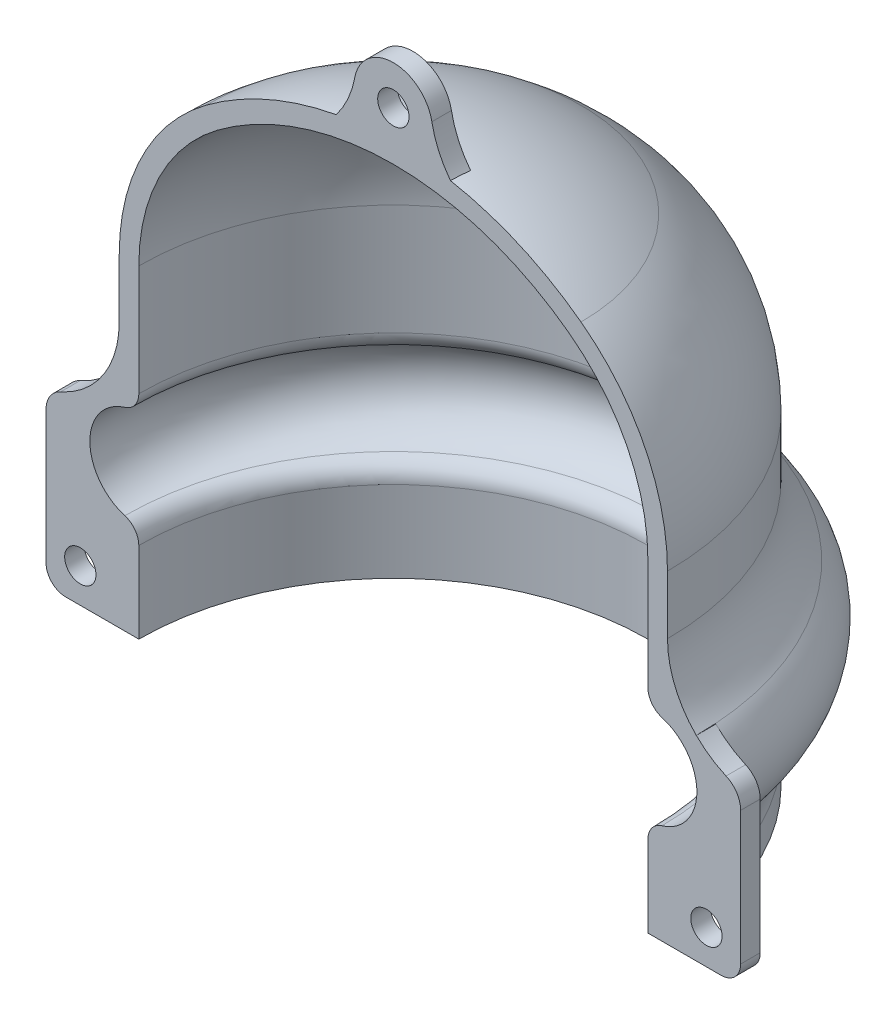
SolidWorks part; units mm, degrees
ref_plane "前视基准面" through (0, 0, 0) normal (0, 0, 1) x (1, 0, 0)
ref_plane "上视基准面" through (0, 0, 0) normal (0, 1, 0) x (1, 0, 0)
ref_plane "右视基准面" through (0, 0, 0) normal (1, 0, 0) x (0, 0, -1)
other "Configuration Table"
sketch "草图1" plane through (0, 0, 0) normal (0, 0, 1) x (1, 0, 0)
  line L0 (0, 65.7347) -> (0, 0) construction
  line L1 (-26, -33.9013) -> (-26, 10) construction
  line L2 (-26, 0) -> (-26, 10)
  line L3 (-26, 0) -> (0, 0) construction
  line L4 (0, 0) -> (0, 55.0111) construction
  line L5 (-26, 20) -> (-26, 33.0166)
  line L6 (-26, 20) -> (-26, 62.4172) construction
  line L7 (-28, 0) -> (-28, 8.2918)
  line L8 (-28, 21.7082) -> (-28, 33.0166)
  line L9 (0, 57.0111) -> (0, 55.0111)
  line L10 (-28, 0) -> (-26, 0)
  arc A0 (-26, 20) -> (-26, 10) centre (-26, 15) ccw
  arc A1 (-17.9734, 49.0366) -> (0, 55.0111) centre (0, 24.9889) cw
  arc A2 (-26, 33.0166) -> (-17.9734, 49.0366) centre (-6, 33.0166) cw
  arc A3 (-28, 21.7082) -> (-28, 8.2918) centre (-26, 15) ccw
  arc A4 (-28, 33.0166) -> (-19.1707, 50.6385) centre (-6, 33.0166) cw
  arc A5 (-19.1707, 50.6385) -> (0, 57.0111) centre (0, 24.9889) cw
  point P15 (-26, 40)
  dimension "D2" = 10
  dimension "D6" = 20
  dimension "D1" = 26
  dimension "D3" = 25
  dimension "D4" = 15
  dimension "D5" = 60
  dimension "D7" = 2
revolve "旋转1" add sketch "草图1" angle 180 about L0
fillet "圆角1" radius 10 2 edges at (0, 8.2918, -28) (0, 21.7082, -28)
sketch "草图2" plane through (0, 0, 0) normal (0, 0, 1) x (1, 0, 0)
  line L0 (-35.4746, 15.5963) -> (-35.4746, 2)
  line L1 (-33.4746, 0) -> (-28, 0)
  line L4 (0, 73.9629) -> (0, -6.6325) construction
  line L5 (-30.9412, 19.9583) -> (-26, 20)
  line L6 (-28, 0) -> (-26, 0) construction
  line L7 (-26, 0) -> (-26, 10) construction
  line L8 (-28, 0) -> (-26, 0)
  line L9 (-26, 0) -> (-26, 10)
  line L10 (26, 0) -> (26, 10)
  line L11 (28, 0) -> (26, 0)
  line L12 (30.9412, 19.9583) -> (26, 20)
  line L13 (33.4746, 0) -> (28, 0)
  line L14 (35.4746, 15.5963) -> (35.4746, 2)
  arc A0 (-30.9412, 19.9583) -> (-28, 27.0416) centre (-38, 27.0416) ccw construction
  arc A1 (-33.9796, 17.8854) -> (-30.9412, 19.9583) centre (-38, 27.0416) ccw
  arc A2 (-33.9796, 17.8854) -> (-35.4746, 15.5963) centre (-32.9746, 15.5963) ccw
  arc A3 (-30.9412, 19.9583) -> (-30.9412, 10.0417) centre (-26, 15) ccw construction
  arc A4 (-35.4746, 2) -> (-33.4746, 0) centre (-33.4746, 2) ccw
  circle A5 centre (-31.9746, 3.5) radius 1.6
  circle A9 centre (0, 60) radius 1.6
  arc A10 (3.932, 60.7345) -> (-3.932, 60.7345) centre (0, 60) ccw
  arc A11 (-10.3234, 53.1804) -> (-3.932, 60.7345) centre (-13.762, 62.5706) ccw
  arc A12 (3.932, 60.7345) -> (10.3234, 53.1804) centre (13.762, 62.5706) ccw
  arc A13 (17.9734, 49.0366) -> (-17.9734, 49.0366) centre (0, 24.9889) ccw construction
  arc A14 (10.3234, 53.1804) -> (-10.3234, 53.1804) centre (0, 24.9889) ccw
  arc A15 (-26, 20) -> (-26, 10) centre (-26, 15) ccw construction
  arc A16 (-26, 20) -> (-26, 10) centre (-26, 15) ccw
  arc A17 (26, 20) -> (26, 10) centre (26, 15) cw
  circle A18 centre (31.9746, 3.5) radius 1.6
  arc A19 (35.4746, 2) -> (33.4746, 0) centre (33.4746, 2) cw
  arc A20 (33.9796, 17.8854) -> (35.4746, 15.5963) centre (32.9746, 15.5963) cw
  arc A21 (33.9796, 17.8854) -> (30.9412, 19.9583) centre (38, 27.0416) cw
  line M1 (26, 0) -> (28, 0)
  line M2 (28, 0) -> (28, 2.9584)
  arc M3 (28, 2.9584) -> (30.9412, 10.0417) centre (38, 2.9584) cw
  arc M4 (30.9412, 10.0417) -> (30.9412, 19.9583) centre (26, 15) ccw
  arc M8 (19.1707, 50.6385) -> (-19.1707, 50.6385) centre (0, 24.9889) ccw
  arc M12 (-30.9412, 19.9583) -> (-30.9412, 10.0417) centre (-26, 15) ccw
  arc M13 (-30.9412, 10.0417) -> (-28, 2.9584) centre (-38, 2.9584) cw
  line M14 (-28, 2.9584) -> (-28, 0)
  line M15 (-28, 0) -> (-26, 0)
  line M16 (-26, 0) -> (-26, 10)
  arc M17 (-26, 10) -> (-26, 20) centre (-26, 15) cw
  arc M20 (-17.9734, 49.0366) -> (17.9734, 49.0366) centre (0, 24.9889) cw
  arc M23 (26, 20) -> (26, 10) centre (26, 15) cw
  line M24 (26, 10) -> (26, 0)
  dimension "D1" = 5
  dimension "D2" = 2
  dimension "D5" = 3.2
  dimension "D6" = 3.2
  dimension "D7" = 8
  dimension "D9" = 20
  dimension "D10" = 20
  dimension "D3" = 3.5
  dimension "D4" = 3.5
  dimension "D8" = 60
extrude "凸台-拉伸1" add sketch "草图2" against normal blind 2 contours L0 A4 L1 A1 A2 A5 M14 M13 M12 | L4 A10 A11 A9 M8 | L4 A11 M8 M20 | L4 A14 A12 M8 | A10 L4 A9 A12 M8 | L5 M12 M13 M14 M15 M16 M17 | L12 M4 M23 M24 M1 M2 M3 | A20 A21 L13 A19 L14 A18 M4 M3 M2
fillet "圆角2" radius 2 2 edges at (0, 10, -26) (0, 20, -26)
